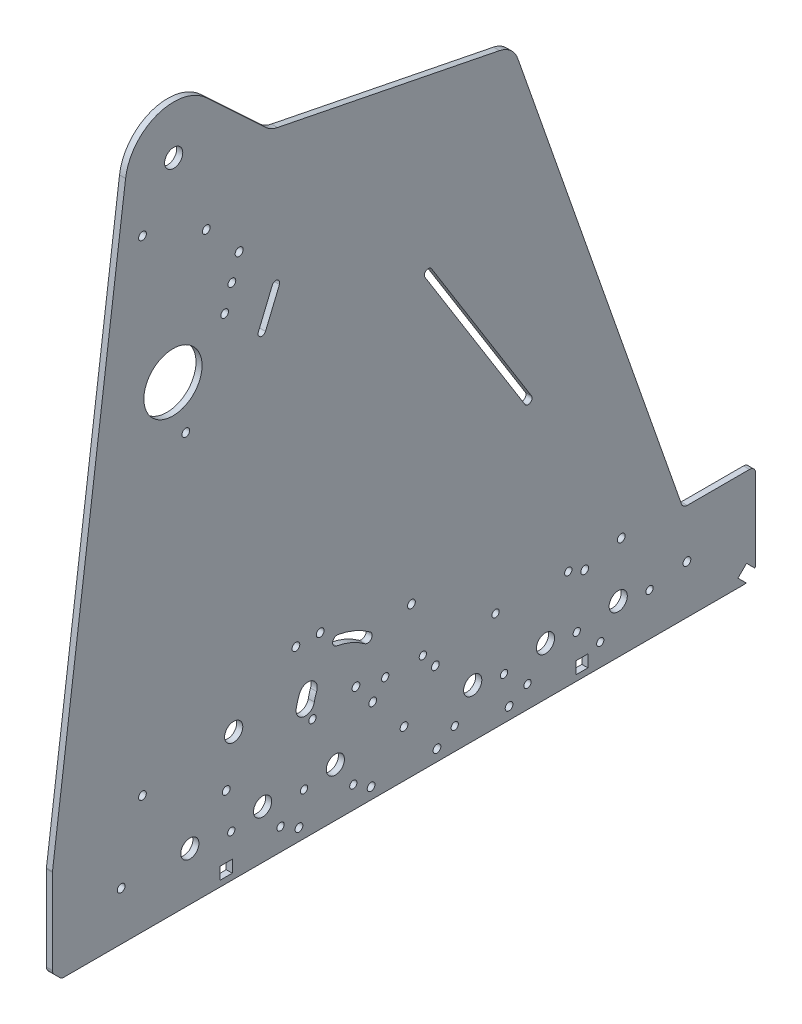
SolidWorks part; units mm, degrees
ref_plane "Front Plane" through (0, 0, 0) normal (0, 0, 1) x (1, 0, 0)
ref_plane "Top Plane" through (0, 0, 0) normal (0, 1, 0) x (1, 0, 0)
ref_plane "Right Plane" through (0, 0, 0) normal (1, 0, 0) x (0, 0, -1)
sketch "Sketch1" plane through (0, 0, 0) normal (1, 0, 0) x (0, 0, -1)
  line L0 (-184.15, -24.6062) -> (184.15, -24.6062)
  line L1 (184.15, -24.6062) -> (184.15, 26.1938)
  line L2 (184.15, 26.1938) -> (146.05, 26.1937)
  line L3 (146.05, 26.1937) -> (57.15, 280.1938)
  line L5 (-145.839, 321.5609) -> (-184.15, 26.1938)
  line L6 (-184.15, 26.1938) -> (-184.15, -24.6062)
  line L7 (-184.15, 350.0437) -> (184.15, 350.0437) construction
  line L8 (57.15, 280.1938) -> (-69.85, 305.5938)
  line L9 (-69.85, 305.5938) -> (-103.3099, 336.854)
  arc A0 (-103.3099, 336.854) -> (-145.839, 321.5609) centre (-120.65, 318.2937) ccw
  point P8 (0, -24.6062)
  dimension "D1" = 368.3
  dimension "D7" = 25.4
  dimension "D2" = 50.8
  dimension "D3" = 38.1
  dimension "D4" = 24.6062
  dimension "D5" = 374.65
  dimension "D6" = 304.8
  dimension "D8" = 342.9
  dimension "D9" = 127
  dimension "D10" = 304.8
  dimension "D11" = 25.4
  dimension "D12" = 127
extrude "Boss-Extrude1" add sketch "Sketch1" along normal blind 3.175
chamfer "Chamfer1" distance 4.7625 angle 45 2 edges at (1.5875, -24.6062, 184.15) (1.5875, -24.6062, -184.15)
fillet "Fillet1" radius 12.7 2 edges at (1.5875, 305.5938, 69.85) (1.5875, 280.1938, -57.15)
fillet "Fillet2" radius 3.175 3 edges at (1.5875, 26.1938, 184.15) (1.5875, 26.1938, -184.15) (1.5875, 26.1937, -146.05)
fillet "Fillet3" radius 3.175 4 edges at (1.5875, -19.8438, -184.15) (1.5875, -24.6062, -179.3875) (1.5875, -19.8437, 184.15) (1.5875, -24.6062, 179.3875)
sketch "Sketch16" plane through (3.175, 0, 0) normal (1, 0, 0) x (0, 0, -1)
  circle A0 centre (112.1746, 0.7937) radius 4.7625
  circle A1 centre (74.0746, 0.7937) radius 4.7625
  circle A2 centre (35.9746, 0.7937) radius 4.7625
  circle A3 centre (-35.9746, 0.7938) radius 4.7625
  circle A4 centre (-74.0746, 0.7938) radius 4.7625
  circle A5 centre (-112.1746, 0.7937) radius 4.7625
  dimension "D1" = 9.525
  dimension "D2" = 9.525
extrude "Cut-Extrude1" cut sketch "Sketch16" against normal up to next
sketch "Sketch25" plane through (3.175, 0, 0) normal (1, 0, 0) x (0, 0, -1)
  circle A0 centre (102.7672, -13.0003) radius 1.905 construction
  circle A1 centre (86.0486, 27.3622) radius 1.905 construction
  circle A2 centre (128.5804, -2.3081) radius 1.905 construction
  circle A3 centre (102.7672, -13.0003) radius 1.905
  circle A4 centre (86.0486, 27.3622) radius 1.905
  circle A5 centre (128.5804, -2.3081) radius 1.905
  circle A6 centre (64.6672, -13.0003) radius 1.905 construction
  circle A8 centre (-9.8486, 27.3622) radius 1.905 construction
  circle A10 centre (-47.9486, 27.3622) radius 1.905 construction
  circle A11 centre (-90.4804, -2.3081) radius 1.905 construction
  circle A12 centre (-64.6672, -13.0003) radius 1.905 construction
  circle A14 centre (-52.3804, -2.3081) radius 1.905 construction
  circle A15 centre (-26.5672, -13.0003) radius 1.905 construction
  circle A16 centre (9.8486, 27.3622) radius 1.905 construction
  circle A17 centre (26.5672, -13.0003) radius 1.905 construction
  circle A18 centre (47.9486, 27.3622) radius 1.905 construction
  circle A19 centre (52.3804, -2.3081) radius 1.905 construction
  circle A20 centre (90.4804, -2.3081) radius 1.905 construction
  circle A21 centre (-9.8486, 27.3622) radius 1.905
  circle A23 centre (-47.9486, 27.3622) radius 1.905
  circle A24 centre (-90.4804, -2.3081) radius 1.905
  circle A25 centre (-64.6672, -13.0003) radius 1.905
  circle A27 centre (-52.3804, -2.3081) radius 1.905
  circle A28 centre (-26.5672, -13.0003) radius 1.905
  circle A29 centre (9.8486, 27.3622) radius 1.905
  circle A30 centre (26.5672, -13.0003) radius 1.905
  circle A31 centre (47.9486, 27.3622) radius 1.905
  circle A32 centre (64.6672, -13.0003) radius 1.905
  circle A33 centre (52.3804, -2.3081) radius 1.905
  circle A34 centre (90.4804, -2.3081) radius 1.905
extrude "Cut-Extrude4" cut sketch "Sketch25" against normal up to next
sketch "Sketch23" plane through (3.175, 0, 0) normal (1, 0, 0) x (0, 0, -1)
  point P0 (-55.0246, -18.3223)
  point P6 (-93.1246, 17.5943)
  point P9 (-17.2515, -18.6426)
  point P12 (-16.4124, 19.3854)
  point P15 (16.4124, 19.3854)
  point P18 (17.2515, -18.6426)
  point P21 (55.0246, -18.3223)
  point P35 (3.8736, 53.6853)
  point P38 (113.7728, 28.6594)
  point P41 (-137.0088, 37.226)
hole_wizard "#8 (0.16) Diameter Hole1" positions "Sketch23" profile "Sketch24" hole size "#8" standard "ANSI Inch" end condition up to next
sketch "Sketch24" plane through (3.175, -18.3223, 55.0246) normal (0, 1, 0) x (0, 0, -1)
  line L0 (0, 0) -> (0, 3.175)
  line L1 (0, 3.175) -> (2.032, 3.175)
  line L2 (2.032, 3.175) -> (2.032, 0)
  line L5 (2.032, 0) -> (0, 0)
  line L11 (0, -6.35) -> (0, 107.95) construction
  dimension "Thru Hole Dia." = 4.064
  dimension "Thru Hole Depth" = 3.175
sketch "Sketch22" plane through (3.175, 0, 0) normal (1, 0, 0) x (0, 0, -1)
  line L0 (-96.2996, -15.1473) -> (-89.9496, -15.1473) construction
  line L1 (-96.2996, -15.1473) -> (-89.9496, -15.1473)
  line L2 (-96.2996, -15.1473) -> (-96.2996, -21.4973)
  line L3 (-96.2996, -21.4973) -> (-89.9496, -21.4973)
  line L4 (-89.9496, -15.1473) -> (-89.9496, -21.4973)
  line L5 (-96.2996, -15.1473) -> (-89.9496, -21.4973) construction
  line L6 (-96.2996, -21.4973) -> (-89.9496, -15.1473) construction
  line L7 (-89.9496, -15.1473) -> (-89.9496, -19.8734) construction
  line L77 (179.3875, -24.6062) -> (183.8776, -20.1161)
  line L78 (179.3875, -24.6062) -> (174.8974, -20.1161)
  line L79 (183.8776, -20.1161) -> (179.3875, -15.626)
  line L80 (174.8974, -20.1161) -> (179.3875, -15.626)
  line L81 (180.3174, -23.6763) -> (183.2201, -20.7737) construction
  line L82 (-178.0724, -24.6062) -> (178.0724, -24.6062) construction
  line L84 (89.9496, -21.4973) -> (96.2996, -21.4973)
  line L85 (89.9496, -21.4973) -> (89.9496, -15.1473)
  line L86 (89.9496, -15.1473) -> (96.2996, -15.1473)
  line L87 (96.2996, -21.4973) -> (96.2996, -15.1473)
  line L88 (89.9496, -21.4973) -> (96.2996, -15.1473) construction
  line L89 (89.9496, -15.1473) -> (96.2996, -21.4973) construction
  point P0 (-93.1246, -18.3223)
  point P19 (93.1246, -18.3223)
  dimension "D1" = 6.35
  dimension "D2" = 6.35
extrude "Cut-Extrude3" cut sketch "Sketch22" against normal up to next
sketch "Sketch21" plane through (3.175, 0, 0) normal (1, 0, 0) x (0, 0, -1)
  circle A0 centre (-148.1579, 0.7937) radius 2.032
  circle A2 centre (0, 0) radius 2.032
  circle A3 centre (148.1579, 0.7938) radius 2.032
  dimension "D1" = 4.064
extrude "Cut-Extrude2" cut sketch "Sketch21" against normal up to next
sketch "Sketch26" plane through (3.175, 0, 0) normal (1, 0, 0) x (0, 0, -1)
  line L0 (-145.839, 321.5609) -> (-184.1236, 26.3971) construction
  line L1 (-178.0724, -24.6062) -> (178.0724, -24.6062) construction
  circle A0 centre (-121.0218, 216.6937) radius 15.24
  dimension "D1" = 30.48
  dimension "D2" = 38.1
  dimension "D3" = 241.3
extrude "Cut-Extrude5" cut sketch "Sketch26" against normal through all
sketch "Sketch27" plane through (3.175, 0, 0) normal (1, 0, 0) x (0, 0, -1)
  circle A0 centre (-120.65, 318.2937) radius 4.7625
  dimension "D1" = 9.525
extrude "Cut-Extrude6" cut sketch "Sketch27" against normal through all
sketch "Sketch28" plane through (3.175, 0, 0) normal (1, 0, 0) x (0, 0, -1)
  line L0 (-120.65, 318.2937) -> (-103.5612, 277.2599) construction
  line L1 (-103.5612, 277.2599) -> (-86.3654, 258.566) construction
  line L2 (-86.3654, 258.566) -> (-90.1612, 246.4465) construction
  line L3 (-90.1612, 246.4465) -> (-93.9569, 234.327) construction
  line L4 (-145.839, 321.5609) -> (-184.1236, 26.3971) construction
  circle A0 centre (-93.9569, 234.327) radius 2.032
  circle A1 centre (-90.1612, 246.4465) radius 2.032
  circle A2 centre (-86.3654, 258.566) radius 2.0955
  circle A3 centre (-103.5612, 277.2599) radius 2.032
  dimension "D4" = 4.064
  dimension "D5" = 4.191
  dimension "D6" = 4.064
  dimension "D1" = 25.4
  dimension "D2" = 44.45
  dimension "D3" = 12.7
  dimension "D7" = 30
  dimension "D8" = 120
  dimension "D9" = 160
extrude "Cut-Extrude7" cut sketch "Sketch28" against normal through all
sketch "Sketch29" plane through (3.175, 0, 0) normal (1, 0, 0) x (0, 0, -1)
  line L0 (-145.839, 321.5609) -> (-184.1236, 26.3971) construction
  line L1 (-67.1375, 233.9197) -> (-74.4276, 216.3198) construction
  line L2 (-65.2602, 233.1421) -> (-72.5503, 215.5422)
  line L3 (-69.0148, 234.6973) -> (-76.305, 217.0974)
  line L4 (-67.1375, 233.9197) -> (-67.1375, 253.7354) construction
  circle A0 centre (-136.9875, 291.0697) radius 2.032
  circle A2 centre (-120.65, 318.2937) radius 4.7625 construction
  arc A4 (-65.2602, 233.1421) -> (-69.0148, 234.6973) centre (-67.1375, 233.9197) ccw
  arc A5 (-76.305, 217.0974) -> (-72.5503, 215.5422) centre (-74.4276, 216.3198) ccw
  point P8 (-70.7826, 225.1198)
  dimension "D1" = 31.75
  dimension "D2" = 4.064
  dimension "D3" = 69.85
  dimension "D4" = 12.7
  dimension "D5" = 57.15
  dimension "D6" = 19.05
  dimension "D7" = 22.5
extrude "Cut-Extrude8" cut sketch "Sketch29" against normal through all
sketch "Sketch30" plane through (3.175, 0, 0) normal (1, 0, 0) x (0, 0, -1)
  circle A8 centre (-89.211, 42.2593) radius 4.7625
  circle A9 centre (-25.1593, 30.6938) radius 2.032
  arc A10 (-51.7173, 35.4892) -> (-50.2741, 40.5715) centre (-25.1593, 30.6938) cw construction
  arc A11 (-54.7652, 42.3379) -> (-56.4665, 36.3468) centre (-25.1593, 30.6938) ccw
  arc A12 (-45.783, 38.8051) -> (-46.9681, 34.6317) centre (-25.1593, 30.6938) ccw
  arc A13 (-45.783, 38.8051) -> (-54.7652, 42.3379) centre (-50.2741, 40.5715) ccw
  arc A14 (-56.4665, 36.3468) -> (-46.9681, 34.6317) centre (-51.7173, 35.4892) ccw
  arc A15 (-34.9881, 56.6661) -> (-19.1131, 49.8125) centre (-41.7582, 19.1724) cw construction
  arc A16 (-17.6789, 51.753) -> (-34.5594, 59.0407) centre (-41.7582, 19.1724) ccw
  arc A17 (-20.5473, 47.8719) -> (-35.4169, 54.2915) centre (-41.7582, 19.1724) ccw
  arc A18 (-20.5473, 47.8719) -> (-17.6789, 51.753) centre (-19.1131, 49.8125) ccw
  arc A19 (-34.5594, 59.0407) -> (-35.4169, 54.2915) centre (-34.9881, 56.6661) ccw
  arc A20 (-19.1131, 49.8125) -> (-34.9881, 56.6661) centre (-41.7582, 19.1724) ccw construction
  circle A21 centre (94.6345, 23.8125) radius 2.032
  circle A22 centre (-56.6241, 64.5541) radius 2.032
  circle A23 centre (-43.9241, 64.5541) radius 2.032
  circle A24 centre (-56.6241, 64.5541) radius 1.905 construction
  circle A25 centre (-43.9241, 64.5541) radius 1.905 construction
  point P7 (-51.1204, 38.0658)
  point P19 (-26.6567, 54.1518)
  point P33 (-56.7148, 64.7837)
  dimension "D2" = 9.652
  dimension "D4" = 4.064
  dimension "D1" = 4.064
  dimension ".375" = 9.525
  dimension "D3" = 4.826
extrude "Cut-Extrude9" cut sketch "Sketch30" against normal through all
sketch "Sketch31" plane through (0, 0, 0) normal (-1, 0, 0) x (0, 0, 1)
  circle A1 centre (114.3, 190.5) radius 2.032
  dimension "D1" = 114.3
  dimension "D6" = 4.064
  dimension "D2" = 190.5
extrude "Cut-Extrude10" cut sketch "Sketch31" against normal through all
sketch "Sketch34" plane through (0, 0, 0) normal (-1, 0, 0) x (0, 0, 1)
  line L0 (-65.024, 115.57) -> (-12.7, 199.39) construction
  line L1 (-66.7477, 116.646) -> (-14.4237, 200.466)
  line L2 (-63.3003, 114.494) -> (-10.9763, 198.314)
  arc A0 (-66.7477, 116.646) -> (-63.3003, 114.494) centre (-65.024, 115.57) ccw
  arc A1 (-10.9763, 198.314) -> (-14.4237, 200.466) centre (-12.7, 199.39) ccw
  point P3 (-38.862, 157.48)
  dimension "D5" = 2.032
  dimension "D1" = 115.57
  dimension "D2" = 65.024
  dimension "D3" = 199.39
  dimension "D4" = 12.7
extrude "Cut-Extrude12" cut sketch "Sketch34" against normal through all
